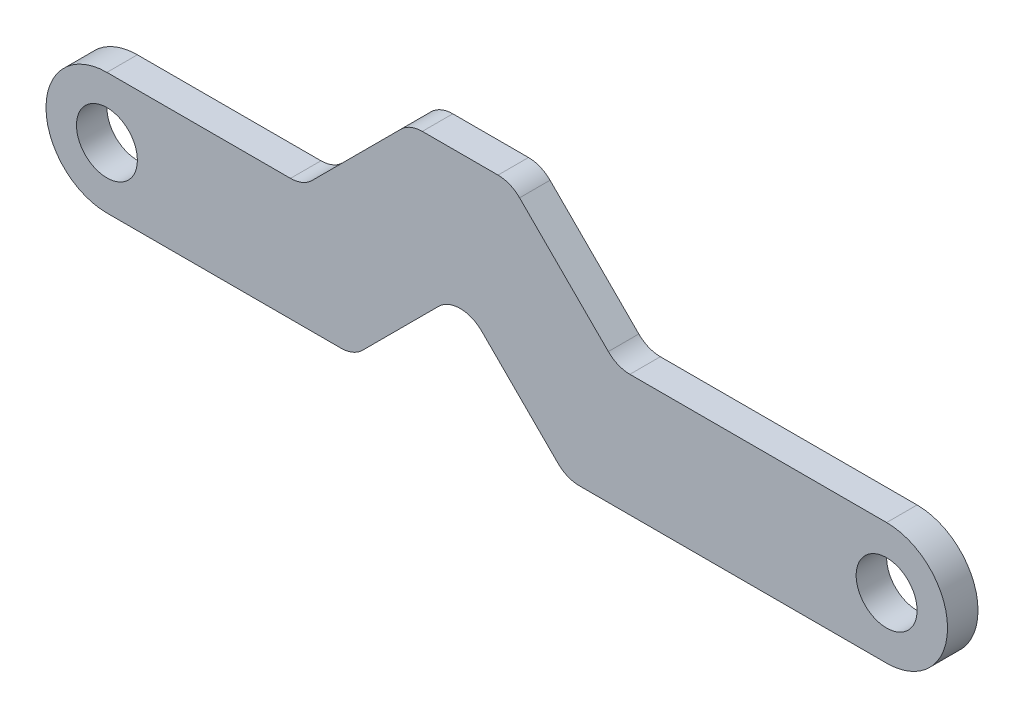
SolidWorks part; units mm, degrees
note: The reader was unsure of these and kept them because the rebuilt part matched: shared geometry of "Sketch".
ref_plane "Спереди" through (0, 0, 0) normal (0, 0, 1) x (1, 0, 0)
ref_plane "Сверху" through (0, 0, 0) normal (0, 1, 0) x (1, 0, 0)
ref_plane "Справа" through (0, 0, 0) normal (1, 0, 0) x (0, 0, -1)
sketch "Эскиз1" plane through (0, 0, 0) normal (0, 0, 1) x (1, 0, 0)
  line L0 (0, 0) -> (-25.5979, 0)
  line L1 (-25.5979, -2) -> (0, -2)
  line L2 (-25.5979, 2) -> (0, 2)
  circle A0 centre (-25.5979, 0) radius 1
  circle A1 centre (0, 0) radius 1
  circle A2 centre (-25.5979, 0) radius 2
  circle A3 centre (0, 0) radius 2
  dimension "D1" = 25.5979
extrude "Бобышка-Вытянуть1" add sketch "Эскиз1" along normal mid plane 1
sketch "Sketch1" plane through (0, 0, 0) normal (0, 0, 1) x (1, 0, 0)
  line L0 (0, 0) -> (-14, 0)
  line L1 (-14, 0) -> (-14, 1.5)
  line L2 (-25.5979, -2) -> (-2.0642, -2)
  line L3 (-14, 0) -> (-25.5979, 0)
  line L7 (-14, 1.5) -> (-20.4712, -4.9712)
  line L11 (0, 2) -> (-30.8022, 2)
  line L12 (-14, 1.5) -> (-7.5288, -4.9712)
  line L13 (-20.4712, -4.9712) -> (-7.5288, -4.9712)
  line L14 (-15.6569, 5.5) -> (-30.1281, -8.9712)
  line L15 (-30.1281, -8.9712) -> (2.1281, -8.9712)
  line L16 (-12.3431, 5.5) -> (2.1281, -8.9712)
  line L17 (-14, 1.5) -> (-14, 5.5)
  line L18 (-14, 5.5) -> (-15.6569, 5.5)
  line L19 (-14, 5.5) -> (-12.3431, 5.5)
  line L21 (-14, 7.1569) -> (-30.1281, -8.9712) construction
  line L22 (-14, 7.1569) -> (2.1281, -8.9712) construction
  point P6 (-9.7278, -2.9956)
  point P9 (-14.7071, 0.7071)
  point P10 (-13.2929, 0.7071)
  point P11 (-21.4142, -2.5858)
  point P15 (-16, 0)
  point P22 (-10, 0)
  dimension "D1" = 4
  dimension "D4" = 14
  dimension "D2" = 1.5
extrude "Extrude1" add sketch "Sketch1" against normal mid plane 1
extrude "Extrude2" cut sketch "Sketch" against normal mid plane 1
sketch "Sketch" plane through (0, 0, 0) normal (0, 0, 1) x (1, 0, 0) same geometry as "Sketch1"
fillet "Fillet8" radius 1 3 edges at (-8.8431, 2, 0) (-14, 1.5, 0) (-19.1569, 2, 0)
fillet "Fillet9" radius 1 4 edges at (-10.5, -2, 0) (-17.5, -2, 0) (-12.3431, 5.5, 0) (-15.6569, 5.5, 0)
